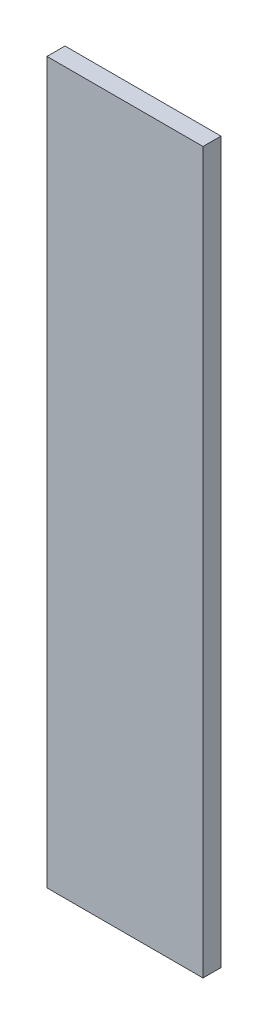
SolidWorks part; units mm, degrees
ref_plane "Front Plane" through (0, 0, 0) normal (0, 0, 1) x (1, 0, 0)
ref_plane "Top Plane" through (0, 0, 0) normal (0, 1, 0) x (1, 0, 0)
ref_plane "Right Plane" through (0, 0, 0) normal (1, 0, 0) x (0, 0, -1)
sketch "Sketch1" plane through (0, 0, 0) normal (0, 0, 1) x (1, 0, 0)
  line L1 (-49.2574, 89.9404) -> (115.8426, 89.9404)
  line L2 (-49.2574, 89.9404) -> (-49.2574, -672.0596)
  line L3 (-49.2574, -672.0596) -> (115.8426, -672.0596)
  line L4 (115.8426, 89.9404) -> (115.8426, -672.0596)
  line L5 (-49.2574, 89.9404) -> (115.8426, -672.0596) construction
  line L6 (-49.2574, -672.0596) -> (115.8426, 89.9404) construction
  point P0 (33.2926, -291.0596)
extrude "Boss-Extrude1" add sketch "Sketch1" along normal blind 19.05 contours L2 L1 L4 L3
